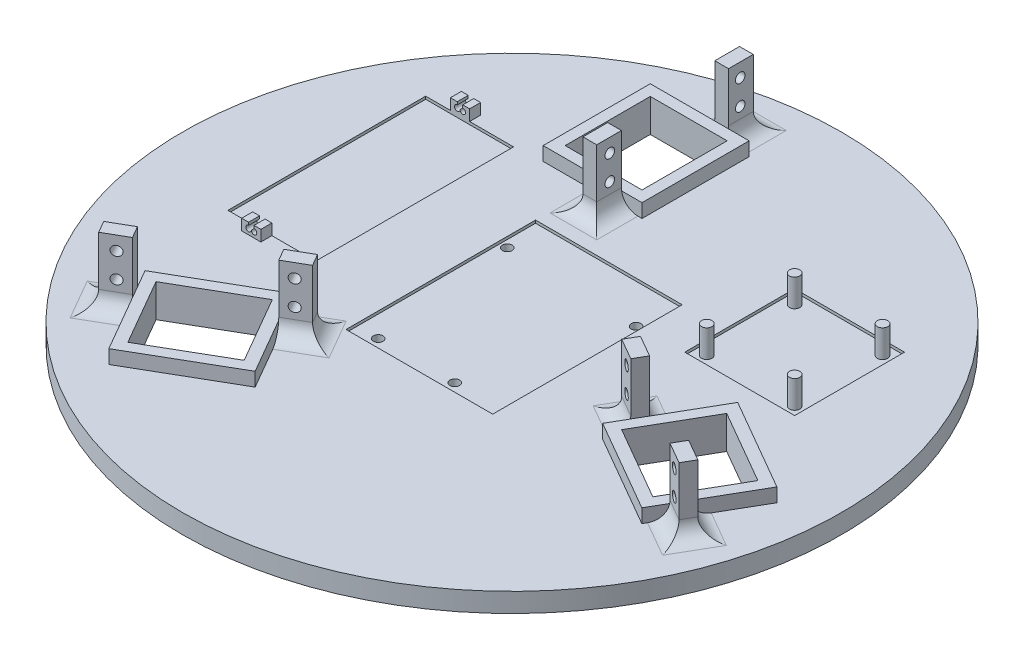
SolidWorks part; units mm, degrees
ref_plane "Front Plane" through (0, 0, 0) normal (0, 0, 1) x (1, 0, 0)
ref_plane "Top Plane" through (0, 0, 0) normal (0, 1, 0) x (1, 0, 0)
ref_plane "Right Plane" through (0, 0, 0) normal (1, 0, 0) x (0, 0, -1)
sketch "Sketch1" plane through (0, 0, 0) normal (0, 1, 0) x (1, 0, 0)
  circle A0 centre (0, 0) radius 120
  dimension "D1" = 240
extrude "Boss-Extrude1" add sketch "Sketch1" along normal blind 7
sketch "Sketch2" plane through (0, 7, 0) normal (0, 1, 0) x (1, 0, 0)
  line L0 (0, 0) -> (-103.923, -60) construction
  line L1 (103.923, -60) -> (0, 0) construction
  line L2 (0, 0) -> (0, 120) construction
  line L3 (-26.317, -67.2134) -> (-60.092, -86.7134)
  line L4 (-26.317, -67.2134) -> (-44.317, -36.0364)
  line L5 (-27.943, 36.5159) -> (25.457, 36.5159)
  line L6 (-27.943, 36.5159) -> (-27.943, -32.4841)
  line L7 (-27.943, -32.4841) -> (25.457, -32.4841)
  line L8 (25.457, 36.5159) -> (25.457, -32.4841)
  line L17 (71.367, 10.8155) -> (105.142, -8.6845)
  line L18 (71.367, 10.8155) -> (53.367, -20.3614)
  line L19 (53.367, -20.3614) -> (87.142, -39.8614)
  line L20 (105.142, -8.6845) -> (87.142, -39.8614)
  line L21 (-44.317, -36.0364) -> (-78.092, -55.5364)
  line L22 (-60.092, -86.7134) -> (-78.092, -55.5364)
  line L23 (-9.05, 95.3978) -> (-9.05, 56.3978)
  line L24 (-9.05, 95.3978) -> (-45.05, 95.3978)
  line L25 (-45.05, 95.3978) -> (-45.05, 56.3978)
  line L26 (-9.05, 56.3978) -> (-45.05, 56.3978)
  line L27 (-62.3857, -36.0184) -> (-61.2607, -37.967) construction
  line L28 (-61.2607, -37.967) -> (-57.8607, -43.8559) construction
  line L29 (54.2669, -31.331) -> (55.3919, -29.3825) construction
  line L30 (55.3919, -29.3825) -> (58.7919, -23.4935) construction
  line L31 (0, 87.283) -> (-2.25, 87.283) construction
  line L32 (-2.25, 87.283) -> (-9.05, 87.283) construction
  line L33 (40.8756, 62.045) -> (40.8756, 22.045)
  line L34 (-87.0297, 55.5963) -> (-55.0297, 55.5963)
  line L35 (-87.0297, 55.5963) -> (-87.0297, -16.4037)
  line L36 (-87.0297, -16.4037) -> (-55.0297, -16.4037)
  line L37 (-55.0297, 55.5963) -> (-55.0297, -16.4037)
  line L38 (-78.0297, 55.5963) -> (-71.0297, 55.5963)
  line L39 (-78.0297, 55.5963) -> (-78.0297, 59.5963)
  line L40 (-78.0297, 59.5963) -> (-71.0297, 59.5963)
  line L41 (-71.0297, 55.5963) -> (-71.0297, 59.5963)
  line L42 (-78.0297, -16.4037) -> (-71.0297, -16.4037)
  line L43 (-78.0297, -16.4037) -> (-78.0297, -20.4037)
  line L44 (-78.0297, -20.4037) -> (-71.0297, -20.4037)
  line L45 (-71.0297, -16.4037) -> (-71.0297, -20.4037)
  line L46 (40.8756, 62.045) -> (80.8756, 62.045)
  line L47 (40.8756, 22.045) -> (80.8756, 22.045)
  line L48 (80.8756, 62.045) -> (80.8756, 22.045)
  circle A4 centre (0, 0) radius 120 construction
  circle A5 centre (0, 0) radius 57.1193 construction
  dimension "D3" = 39
  dimension "D4" = 36
  dimension "D5" = 39
  dimension "D6" = 36
  dimension "D27" = 114.2387
  dimension "D1" = 53.4
  dimension "D2" = 69
  dimension "D7" = 39
  dimension "D8" = 36
  dimension "D9" = 120
  dimension "D10" = 120
  dimension "D11" = 2.25
  dimension "D12" = 6.8
  dimension "D13" = 2.25
  dimension "D14" = 6.8
  dimension "D15" = 2.25
  dimension "D16" = 6.8
  dimension "D17" = 72
  dimension "D18" = 32
  dimension "D19" = 4
  dimension "D20" = 4
  dimension "D21" = 7
  dimension "D22" = 7
  dimension "D23" = 40
  dimension "D24" = 40
  dimension "D25" = 9
  dimension "D26" = 9
extrude "Cut-Extrude3" cut sketch "Sketch2" against normal blind 1 contours L37 L34 L35 L36 | L8 L5 L6 L7 | L48 L46 L33 L47 region at (-1.243, 7, -2.0159) region at (60.8756, 7, -42.045) region at (-71.0297, 7, -19.5963)
extrude "Boss-Extrude2" add sketch "Sketch2<5>" along normal blind 5 contours L26 L23 L24 L25 | L22 L3 L4 L21 | L20 L17 L18 L19 region at (-52.2045, 7, 61.3749) region at (79.2545, 7, 14.5229) region at (-27.05, 7, -75.8978)
sketch "Sketch2<5>" plane through (0, 7, 0) normal (0, 1, 0) x (1, 0, 0) same geometry as "Sketch2"
sketch "Sketch3" plane through (0, 7, 0) normal (0, 1, 0) x (1, 0, 0)
  line L0 (-60.092, -86.7134) -> (-74.342, -62.0316) construction
  line L1 (-60.092, -86.7134) -> (-78.092, -55.5364) construction
  line L2 (-74.342, -62.0316) -> (-82.1362, -66.5316) construction
  line L3 (-74.342, -62.0316) -> (-82.1362, -66.5316)
  line L4 (-74.342, -62.0316) -> (-71.842, -66.3618)
  line L5 (-82.1362, -66.5316) -> (-79.6362, -70.8618)
  line L6 (-71.842, -66.3618) -> (-79.6362, -70.8618)
  line L9 (-40.567, -42.5316) -> (-32.7727, -38.0316)
  line L10 (-40.567, -42.5316) -> (-38.067, -46.8618)
  line L11 (-32.7727, -38.0316) -> (-30.2727, -42.3618)
  line L12 (-38.067, -46.8618) -> (-30.2727, -42.3618)
  line L13 (-26.317, -67.2134) -> (-44.317, -36.0364) construction
  dimension "D1" = 28.5
  dimension "D3" = 5
  dimension "D4" = 9
extrude "Boss-Extrude3" add sketch "Sketch3" along normal blind 24
fillet "Fillet1" radius 6 6 edges at (-36.6698, 7, 40.2816) (-34.1698, 7, 44.6118) (-78.2391, 7, 64.2816) (-75.7391, 7, 68.6118) (-31.5227, 7, 40.1967) (-80.8862, 7, 68.6967)
sketch "Sketch4" plane through (10.775, 0, 18.6628) normal (0.5, 0, 0.866) x (0.866, 0, -0.5)
  line L2 (-56.3978, 31) -> (-56.3978, 13) construction
  line L3 (-95.3978, 31) -> (-95.3978, 13) construction
  line L5 (-104.3978, 31) -> (-95.3978, 31) construction
  circle A0 centre (-52.1478, 26) radius 1.75
  circle A1 centre (-52.1478, 17) radius 1.75
  circle A2 centre (-99.6478, 26) radius 1.75
  circle A3 centre (-99.6478, 17) radius 1.75
  dimension "D1" = 3.5
  dimension "D3" = 3.5
  dimension "D7" = 3.5
  dimension "D8" = 3.5
  dimension "D2" = 5
  dimension "D4" = 9
  dimension "D5" = 9
  dimension "D9" = 4.25
  dimension "D10" = 4.25
extrude "Cut-Extrude4" cut sketch "Sketch4" against normal up to next
extrude "Boss-Extrude4" add sketch "Sketch2<6>" along normal blind 3 contours L34 L41 L40 L39 | L45 L36 L43 L44 region at (-74.5297, 7, -57.5963) region at (-74.5297, 7, 18.4037)
sketch "Sketch2<6>" plane through (0, 7, 0) normal (0, 1, 0) x (1, 0, 0) same geometry as "Sketch2"
sketch "Sketch10" plane through (0, 0, -59.5963) normal (0, 0, -1) x (-1, 0, 0)
  line L3 (73.5297, 10) -> (75.5297, 10)
  line L4 (78.0297, 10) -> (71.0297, 10) construction
  line L5 (78.0297, 10) -> (78.0297, 7) construction
  line L6 (71.0297, 10) -> (71.0297, 7) construction
  arc A0 (73.5297, 10) -> (74.5297, 8.9964) centre (73.5297, 9) ccw
  arc A1 (74.5297, 8.9964) -> (75.5297, 10) centre (75.5297, 9) ccw
  point P11 (74.5297, 10)
  dimension "D1" = 2
  dimension "D2" = 2
  dimension "D3" = 0
  dimension "D4" = 7
  dimension "D5" = 3.5
extrude "Cut-Extrude7" cut sketch "Sketch10" against normal up to surface (80 mm away) up to face at (-74.5297, 8.5, 20.4037)
sketch "Sketch11" plane through (0, 10, 0) normal (0, 1, 0) x (1, 0, 0)
  line L0 (-74.5297, 55.5963) -> (-72.5297, 55.5963) construction
  line L1 (-75.5297, 59.5963) -> (-78.0297, 59.5963)
  line L2 (-75.5297, 59.5963) -> (-75.5297, 55.5963)
  line L3 (-75.5297, 55.5963) -> (-78.0297, 55.5963)
  line L4 (-78.0297, 59.5963) -> (-78.0297, 55.5963)
  line L5 (-73.5297, 55.5963) -> (-71.0297, 55.5963)
  line L6 (-73.5297, 55.5963) -> (-73.5297, 59.5963)
  line L7 (-73.5297, 59.5963) -> (-71.0297, 59.5963)
  line L8 (-71.0297, 55.5963) -> (-71.0297, 59.5963)
  line L10 (-71.0297, -20.4037) -> (-73.5297, -20.4037)
  line L11 (-71.0297, -20.4037) -> (-71.0297, -16.4037)
  line L12 (-71.0297, -16.4037) -> (-73.5297, -16.4037)
  line L13 (-73.5297, -20.4037) -> (-73.5297, -16.4037)
  line L14 (-75.5297, -16.4037) -> (-78.0297, -16.4037)
  line L15 (-75.5297, -16.4037) -> (-75.5297, -20.4037)
  line L16 (-75.5297, -20.4037) -> (-78.0297, -20.4037)
  line L17 (-78.0297, -16.4037) -> (-78.0297, -20.4037)
extrude "Boss-Extrude5" add sketch "Sketch11" along normal blind 1
sketch "Sketch12" plane through (0, 6, 0) normal (0, 1, 0) x (1, 0, 0)
  line L0 (60.8756, 62.045) -> (60.8756, -49937.955) construction
  line L1 (40.8756, 62.045) -> (80.8756, 62.045) construction
  line L2 (40.8756, 42.045) -> (50040.8756, 42.045) construction
  line L3 (40.8756, 62.045) -> (40.8756, 22.045) construction
  line L4 (44.8756, 58.045) -> (76.8756, 58.045) construction
  line L5 (44.8756, 26.045) -> (76.8756, 26.045) construction
  line L6 (44.8756, 58.045) -> (44.8756, 26.045) construction
  circle A0 centre (44.8756, 58.045) radius 1.9
  circle A1 centre (76.8756, 58.045) radius 1.9
  circle A2 centre (76.8756, 26.045) radius 1.9
  circle A3 centre (44.8756, 26.045) radius 1.9
  point P6 (60.8756, 62.045)
  point P11 (40.8756, 42.045)
  point P14 (60.8756, 58.045)
  point P19 (44.8756, 42.045)
  dimension "D1" = 3.8
  dimension "D2" = 3.8
  dimension "D3" = 32
  dimension "D4" = 0
  dimension "D5" = 32
  dimension "D6" = 0
extrude "Boss-Extrude6" add sketch "Sketch12" along normal blind 10
sketch "Sketch13" plane through (0, 7, 0) normal (0, 1, 0) x (1, 0, 0)
  line L12 (99.6778, -10.1486) -> (72.8311, 5.3514)
  line L13 (72.8311, 5.3514) -> (58.8311, -18.8973)
  line L14 (58.8311, -18.8973) -> (85.6778, -34.3973)
  line L15 (85.6778, -34.3973) -> (99.6778, -10.1486)
  line L26 (-41.05, 60.3978) -> (-13.05, 60.3978)
  line L27 (-13.05, 60.3978) -> (-13.05, 91.3978)
  line L28 (-13.05, 91.3978) -> (-41.05, 91.3978)
  line L29 (-41.05, 91.3978) -> (-41.05, 60.3978)
  line L32 (-41.05, 60.3978) -> (-13.05, 60.3978)
  line L33 (-13.05, 60.3978) -> (-13.05, 91.3978)
  line L34 (-13.05, 91.3978) -> (-41.05, 91.3978)
  line L47 (-41.05, 91.3978) -> (-41.05, 60.3978)
  line L48 (-58.6278, -81.2493) -> (-31.7811, -65.7493)
  line L49 (-31.7811, -65.7493) -> (-45.7811, -41.5006)
  line L50 (-45.7811, -41.5006) -> (-72.6278, -57.0006)
  line L51 (-72.6278, -57.0006) -> (-58.6278, -81.2493)
  point P15 (0, 0)
  dimension "D1" = 4
  dimension "D2" = 3
extrude "Cut-Extrude8" cut sketch "Sketch13" against normal through all and the other way through all
pattern_circular "CirPattern2" count 3 over 360 about axis through (0, 7, 0) along (0, -1, 0) of "Fillet1", "Boss-Extrude3", "Cut-Extrude4" reverse direction yes
sketch "Sketch15" plane through (0, 6, 0) normal (0, 1, 0) x (1, 0, 0)
  line L0 (22.857, 22.3159) -> (-25.343, 22.3159) construction
  line L1 (-1.243, 22.3159) -> (-1.243, 36.5159) construction
  line L2 (-27.943, 36.5159) -> (25.457, 36.5159) construction
  line L3 (-27.943, -32.4841) -> (25.457, -32.4841) construction
  circle A0 centre (-20.243, -28.4841) radius 1.75
  circle A1 centre (7.657, -28.4841) radius 1.75
  circle A2 centre (22.857, 22.3159) radius 1.75
  circle A3 centre (-25.343, 23.6159) radius 1.75
  dimension "D4" = 3.5
  dimension "D1" = 27.9
  dimension "D2" = 50.8
  dimension "D3" = 1.3
  dimension "D5" = 4
  dimension "D6" = 15.2
  dimension "D7" = 5.1
extrude "Cut-Extrude9" cut sketch "Sketch15" against normal through all
sketch "Sketch16" plane through (0, 6, 0) normal (0, 1, 0) x (1, 0, 0)
  line L1 (-27.943, 36.5159) -> (25.457, 36.5159)
  line L2 (-27.943, 36.5159) -> (-27.943, -32.4841)
  line L3 (-27.943, -32.4841) -> (25.457, -32.4841)
  line L4 (25.457, 36.5159) -> (25.457, -32.4841)
extrude "Cut-Extrude10" cut sketch "Sketch16" along normal blind 3 from surface starting at face at (-25.343, 0, -21.8659)
